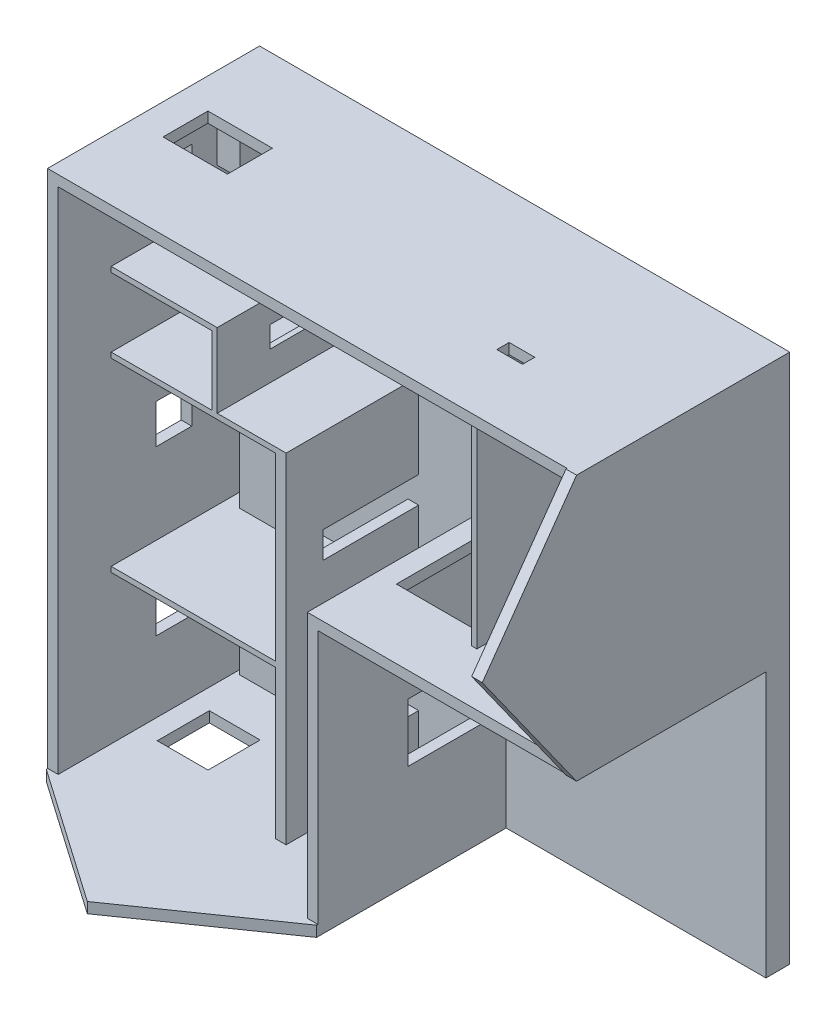
SolidWorks part; units mm, degrees
ref_plane "Front Plane" through (0, 0, 0) normal (0, 0, 1) x (1, 0, 0)
ref_plane "Top Plane" through (0, 0, 0) normal (0, 1, 0) x (1, 0, 0)
ref_plane "Right Plane" through (0, 0, 0) normal (1, 0, 0) x (0, 0, -1)
sketch "Sketch1" plane through (0, 0, 0) normal (0, 0, 1) x (1, 0, 0)
  line L0 (50, 50) -> (50, 48)
  line L1 (-50, -50) -> (50, -50)
  line L2 (-50, -50) -> (-50, 50)
  line L3 (-50, 50) -> (50, 50)
  line L4 (50, -50) -> (50, 50)
  line L5 (-50, -50) -> (50, 50) construction
  line L6 (-50, 50) -> (50, -50) construction
  line L7 (50, 48) -> (-50, 48)
  line L8 (50, 50) -> (50, 48)
  line L9 (-50, 48) -> (-48, 48)
  line L10 (-50, -50) -> (-48, -50)
  line L11 (-48, -50) -> (-48, 48)
  line L12 (50, 50) -> (50, 0)
  line L13 (50, 0) -> (20, 0)
  line L14 (20, 0) -> (20, 50)
  line L15 (-50, -50) -> (-15, -50)
  line L16 (50, 0) -> (50, 2)
  line L17 (50, 2) -> (20, 2)
  line L18 (50, 0) -> (48, 0)
  line L19 (48, 0) -> (48, 50)
  line L20 (-15, -50) -> (-15, 16)
  line L21 (-15, -17) -> (-50, -17)
  line L22 (-50, 16) -> (-15, 16)
  line L23 (-15, -50) -> (1, -50)
  line L24 (1, -50) -> (1, 0)
  line L25 (1, 0) -> (20, 0)
  line L26 (20, 2) -> (1, 2)
  line L27 (1, 2) -> (1, 0)
  line L28 (1, -50) -> (1, -48)
  line L29 (1, -48) -> (-50, -48)
  line L30 (-15, -50) -> (-17, -50)
  line L31 (-17, -50) -> (-17, 16)
  line L32 (20, 50) -> (21, 50)
  line L33 (21, 50) -> (21, 0)
  line L34 (-15, 16) -> (-15, 15)
  line L35 (-15, 15) -> (-50, 15)
  line L36 (-15, -17) -> (-15, -18)
  line L37 (-15, -18) -> (-50, -18)
  line L38 (1, -50) -> (-1, -50)
  line L39 (-1, -50) -> (-1, 0)
  line L40 (1, 2) -> (-1, 2)
  line L41 (-1, 2) -> (-1, 0)
  point P0 (0, 0)
  dimension "D1" = 100
  dimension "D2" = 100
  dimension "D3" = 2
  dimension "D4" = 2
  dimension "D5" = 2
  dimension "D6" = 50
  dimension "D7" = 30
  dimension "D8" = 2
  dimension "D9" = 2
  dimension "D10" = 35
  dimension "D11" = 33
  dimension "D12" = 33
  dimension "D13" = 16
  dimension "D14" = 50
  dimension "D15" = 2
  dimension "D16" = 2
  dimension "D17" = 1
  dimension "D18" = 1
  dimension "D19" = 1
  dimension "D20" = 2
  dimension "D21" = 50
extrude "Boss-Extrude1" add sketch "Sketch1" along normal blind 40 contours L1 L31 L29 L11 | L11 L29 L2 L1 | L31 L15 L20 L29 | L1 L39 L29 L20 | L39 L23 L24 L29 | L40 L41 L39 L29 L24 L27 region at (0, -49, 0) region at (-8, -49, 0) region at (0, -23, 0) region at (-16, -49, 0) region at (-32.5, -49, 0) region at (-49, -49, 0)
extrude "Boss-Extrude3" add sketch "Sketch1<19>" along normal blind 40 contours L11 L37 L2 L29 | L11 L35 L2 L21 | L37 L11 L21 L2 | L2 L22 L11 L7 | L35 L11 L22 L2 region at (-49, 32, 0) region at (-49, 15.5, 0) region at (-49, -1, 0) region at (-49, -17.5, 0) region at (-49, -33, 0)
sketch "Sketch1<19>" plane through (0, 0, 0) normal (0, 0, 1) x (1, 0, 0) same geometry as "Sketch1"
extrude "Boss-Extrude4" add sketch "Sketch1<20>" along normal blind 40 contours L7 L14 L3 L2 | L3 L33 L7 L19 | L33 L3 L14 L7 region at (34.5, 49, 0) region at (20.5, 49, 0) region at (-15, 49, 0)
sketch "Sketch1<20>" plane through (0, 0, 0) normal (0, 0, 1) x (1, 0, 0) same geometry as "Sketch1"
extrude "Boss-Extrude5" add sketch "Sketch1<21>" along normal blind 40 contours L19 L7 L0 L3 | L19 L17 L12 L7 | L19 L13 L4 L17 | L17 L33 L13 L19 | L26 L27 L25 L14 | L33 L17 L14 L13 region at (49, 49, 0) region at (49, 25, 0) region at (49, 1, 0) region at (34.5, 1, 0) region at (20.5, 1, 0) region at (10.5, 1, 0)
sketch "Sketch1<21>" plane through (0, 0, 0) normal (0, 0, 1) x (1, 0, 0) same geometry as "Sketch1"
extrude "Boss-Extrude6" add sketch "Sketch1<23>" along normal blind 30 contours L35 L31 L22 L11 region at (-32.5, 15.5, 0)
sketch "Sketch1<23>" plane through (0, 0, 0) normal (0, 0, 1) x (1, 0, 0) same geometry as "Sketch1"
extrude "Boss-Extrude7" add sketch "Sketch1<28>" along normal blind 30 contours L20 L35 L31 L21 | L35 L20 L22 L31 | L20 L37 L31 L29 region at (-16, 15.5, 0) region at (-16, -33, 0) region at (-16, -1, 0)
sketch "Sketch1<28>" plane through (0, 0, 0) normal (0, 0, 1) x (1, 0, 0) same geometry as "Sketch1"
extrude "Boss-Extrude9" add sketch "Sketch1<31>" along normal blind 5 contours L31 L35 L11 L21 | L31 L37 L11 L29 | L41 L40 L26 L14 L7 L11 L22 L20 L29 L39 | L7 L33 L17 L19 region at (34.5, 25, 0) region at (-10.3503, 17.2139, 0) region at (-32.5, -1, 0) region at (-32.5, -33, 0)
sketch "Sketch1<31>" plane through (0, 0, 0) normal (0, 0, 1) x (1, 0, 0) same geometry as "Sketch1"
sketch "Sketch5" plane through (0, 0, 5) normal (0, 0, 1) x (1, 0, 0)
  line L0 (-48, -17) -> (-48, -18)
  line L1 (-48, -18) -> (-17, -18)
  line L2 (-17, -18) -> (-17, -17)
  line L3 (-17, -17) -> (-48, -17)
extrude "Boss-Extrude10" add sketch "Sketch5" against normal blind 5
sketch "Sketch7" plane through (0, -17, 0) normal (0, -1, 0) x (1, 0, 0)
  line L0 (-17, 30) -> (-15, 30)
  line L7 (-17, 5) -> (-17, 0)
  line L8 (-17, 0) -> (-15, 0)
  line L9 (-15, 0) -> (-15, 5)
  line L10 (-15, 5) -> (-15, 30)
  line L11 (-15, 30) -> (-17, 30)
  line L12 (-17, 30) -> (-17, 5)
  line L13 (-17, 5) -> (-17, 0)
  line L14 (-17, 0) -> (-15, 0)
  line L15 (-15, 0) -> (-15, 5)
  line L16 (-15, 5) -> (-15, 30)
  line L18 (-17, 30) -> (-17, 5)
  dimension "D1" = 0
extrude "Boss-Extrude15" add sketch "Sketch7" along normal blind 5 contours L13 L14 L15 L16 L0 L18
sketch "Sketch8" plane through (-48, 0, 0) normal (1, 0, 0) x (0, 0, -1)
  line L0 (-5, -48) -> (-5, -19)
  line L1 (-5, -48) -> (-5, 15) construction
  line L2 (-5, -19) -> (-30, -19)
  line L3 (-40, -48) -> (-40, 48) construction
  line L4 (-40, -19) -> (-40, -20)
  line L5 (-5, -19) -> (-5, -20)
  line L9 (-5, -20) -> (-30, -20)
  line L10 (-30, -19) -> (-30, -20)
  dimension "D1" = 29
  dimension "D2" = 25
extrude "Boss-Extrude16" add sketch "Sketch8" along normal blind 31 contours L2 L10 L9 L0 region at (-48, -19.5, 17.5)
sketch "Sketch9" plane through (0, 0, 0) normal (0, 0, -1) x (-1, 0, 0)
  line L0 (-20, 48) -> (-21, 48)
  line L1 (-21, 48) -> (-21, 2)
  line L2 (-21, 2) -> (-20, 2)
  line L3 (-20, 2) -> (-20, 48)
extrude "Boss-Extrude17" add sketch "Sketch9" against normal blind 30
sketch "Sketch10" plane through (0, 0, 5) normal (0, 0, 1) x (1, 0, 0)
  line L0 (-48, 16) -> (-28, 16)
  line L1 (-48, 16) -> (-15, 16) construction
  line L2 (-28, 16) -> (-28, 30)
  line L3 (-28, 30) -> (-48, 30)
  line L4 (-48, 16) -> (-48, 48) construction
  line L5 (-48, 30) -> (-48, 29)
  line L6 (-48, 29) -> (-28, 29)
  line L7 (-28, 16) -> (-29, 16)
  line L8 (-29, 16) -> (-29, 29)
  line M6 (-48, 48) -> (-48, 16)
  dimension "D1" = 20
  dimension "D2" = 14
  dimension "D3" = 1
  dimension "D4" = 1
extrude "Boss-Extrude18" add sketch "Sketch10" along normal blind 25 contours L6 L2 L3 M6 | L8 L0 L2 L6 region at (-28.5, 22.5, 5) region at (-38, 29.5, 5)
sketch "Sketch11" plane through (-15, 0, 0) normal (1, 0, 0) x (0, 0, -1)
  line L0 (-5, -38.5606) -> (-5, -33.5606)
  line L1 (-5, -48) -> (-5, 16) construction
  line L2 (-5, -33.5606) -> (-23, -33.5606)
  line L3 (-5, -38.5606) -> (-23, -38.5606)
  line L4 (-23, -38.5606) -> (-23, -33.5606)
  line L5 (-5, 0) -> (-23, 0)
  line L6 (-23, 0) -> (-23, -5)
  line L7 (-23, -5) -> (-5, -5)
  line M8 (-5, -48) -> (-5, 16)
  dimension "D1" = 5
  dimension "D2" = 18
  dimension "D3" = 5
  dimension "D4" = 18
extrude "Cut-Extrude1" cut sketch "Sketch11" against normal blind 25 contours L4 L3 L2 M8 | L6 L7 L5 M8 region at (-15, -36.0606, 14) region at (-15, -2.5, 14)
sketch "Sketch12" plane through (-28, 0, 0) normal (1, 0, 0) x (0, 0, -1)
  line L0 (-5, 21.4951) -> (-5, 25.4951)
  line L1 (-5, 16) -> (-5, 30) construction
  line L2 (-5, 25.4951) -> (-20, 25.4951)
  line L3 (-20, 25.4951) -> (-20, 21.4951)
  line L4 (-20, 21.4951) -> (-5, 21.4951)
  dimension "D1" = 4
  dimension "D2" = 15
extrude "Cut-Extrude2" cut sketch "Sketch12" against normal blind 17
sketch "Sketch13" plane through (21, 0, 0) normal (1, 0, 0) x (0, 0, -1)
  line L0 (-5, 2) -> (-5, 7)
  line L1 (-5, 48) -> (-5, 2) construction
  line L2 (-5, 7) -> (-20, 7)
  line L3 (-20, 7) -> (-20, 2)
  line L4 (-30, 2) -> (-5, 2) construction
  line L5 (-20, 2) -> (-5, 2)
  dimension "D1" = 5
  dimension "D2" = 15
extrude "Cut-Extrude3" cut sketch "Sketch13" against normal blind 17
sketch "Sketch15" plane through (0, 2, 0) normal (0, 1, 0) x (1, 0, 0)
  line L0 (2.7962, -5) -> (13.7962, -5)
  line L1 (48, -5) -> (-1, -5) construction
  line L2 (13.7962, -5) -> (13.7962, -23)
  line L3 (13.7962, -23) -> (2.7962, -23)
  line L4 (2.7962, -23) -> (2.7962, -5)
  dimension "D1" = 11
  dimension "D2" = 18
extrude "Cut-Extrude7" cut sketch "Sketch15" against normal blind 22
sketch "Sketch17" plane through (0, 0, 0) normal (0, -1, 0) x (1, 0, 0)
  line L0 (50, 0) -> (50, 5)
  line L1 (50, 40) -> (50, 0) construction
  line L2 (50, 5) -> (1, 5)
  line L3 (1, 40) -> (1, 0) construction
  line L4 (1, 5) -> (1, 0)
  line L5 (50, 0) -> (1, 0) construction
  line L6 (50, 0) -> (1, 0)
  dimension "D1" = 5
extrude "Boss-Extrude20" add sketch "Sketch17" along normal blind 50
sketch "Sketch23" plane through (1, 0, 0) normal (1, 0, 0) x (0, 0, -1)
  line L0 (-5, -30.6786) -> (-23, -30.6786)
  line L1 (-5, -50) -> (-5, 0) construction
  line L2 (-23, -30.6786) -> (-23, -19.6786)
  line L3 (-23, -19.6786) -> (-5, -19.6786)
  line L4 (-5, -30.6786) -> (-5, -19.6786)
  dimension "D1" = 18
  dimension "D2" = 11
extrude "Cut-Extrude10" cut sketch "Sketch23" against normal blind 6
sketch "Sketch24" plane through (0, 0, 0) normal (0, -1, 0) x (1, 0, 0)
  line L0 (13.7962, 5) -> (17.6537, 5)
  line L1 (50, 5) -> (13.7962, 5) construction
  line L2 (17.6537, 5) -> (17.6537, 23)
  line L3 (17.6537, 23) -> (13.7962, 23)
  line L4 (13.7962, 23) -> (13.7962, 5)
  dimension "D1" = 18
extrude "Cut-Extrude11" cut sketch "Sketch24" against normal blind 6
sketch "Sketch25" plane through (0, 0, 0) normal (0, -1, 0) x (1, 0, 0)
  line L0 (17.6537, 23) -> (17.6537, 27)
  line L1 (17.6537, 27) -> (2.7962, 27)
  line L2 (2.7962, 27) -> (2.7962, 23)
  line L3 (2.7962, 23) -> (17.6537, 23)
  dimension "D1" = 4
extrude "Cut-Extrude12" cut sketch "Sketch25" against normal blind 6
sketch "Sketch26" plane through (0, 0, 0) normal (0, -1, 0) x (1, 0, 0)
  line L0 (27.3061, 27.4895) -> (39.6317, 27.4895)
  line L1 (39.6317, 27.4895) -> (39.6317, 19.0347)
  line L2 (39.6317, 19.0347) -> (27.3061, 19.0347)
  line L3 (27.3061, 19.0347) -> (27.3061, 27.4895)
extrude "Cut-Extrude13" cut sketch "Sketch26" against normal blind 6
sketch "Sketch29" plane through (-50, 0, 0) normal (-1, 0, 0) x (0, 0, 1)
  line L5 (14.7979, 3.7003) -> (21.5327, 3.7003)
  line L6 (14.7979, 3.7003) -> (14.7979, -3.7003)
  line L11 (14.7979, -3.7003) -> (21.5327, -3.7003)
  line L12 (21.5327, 3.7003) -> (21.5327, -3.7003)
  line L17 (14.7979, 3.7003) -> (21.5327, -3.7003) construction
  line L18 (14.7979, -3.7003) -> (21.5327, 3.7003) construction
  line L19 (14.7979, -27.6046) -> (21.5327, -27.6046)
  line L20 (14.7979, -27.6046) -> (14.7979, -34.6008)
  line L21 (14.7979, -34.6008) -> (21.5327, -34.6008)
  line L22 (21.5327, -27.6046) -> (21.5327, -34.6008)
  line L23 (14.7979, -27.6046) -> (21.5327, -34.6008) construction
  line L24 (14.7979, -34.6008) -> (21.5327, -27.6046) construction
  line L25 (14.7979, 35.5253) -> (21.5327, 35.5253)
  line L26 (14.7979, 35.5253) -> (14.7979, 42.3474)
  line L27 (14.7979, 42.3474) -> (21.5327, 42.3474)
  line L28 (21.5327, 35.5253) -> (21.5327, 42.3474)
  line L29 (14.7979, 35.5253) -> (21.5327, 42.3474) construction
  line L30 (14.7979, 42.3474) -> (21.5327, 35.5253) construction
  point P0 (18.1653, 0)
  point P5 (18.1653, -31.1027)
  point P10 (18.1653, 38.9363)
extrude "Cut-Extrude18" cut sketch "Sketch29" against normal blind 6
sketch "Sketch30" plane through (0, -50, 0) normal (0, -1, 0) x (1, 0, 0)
  line L1 (-44.162, 25.1479) -> (-34.5784, 25.1479)
  line L2 (-44.162, 25.1479) -> (-44.162, 15.3213)
  line L3 (-44.162, 15.3213) -> (-34.5784, 15.3213)
  line L4 (-34.5784, 25.1479) -> (-34.5784, 15.3213)
  line L5 (-44.162, 25.1479) -> (-34.5784, 15.3213) construction
  line L6 (-44.162, 15.3213) -> (-34.5784, 25.1479) construction
  point P0 (-39.3702, 20.2346)
extrude "Cut-Extrude19" cut sketch "Sketch30" against normal blind 6
sketch "Sketch32" plane through (0, 0, 5) normal (0, 0, 1) x (1, 0, 0)
  line L0 (-17, -20) -> (-48, -20) construction
  line L1 (-42.7475, 2.9062) -> (-33.4614, 2.9062)
  line L2 (-42.7475, 2.9062) -> (-42.7475, -16.3961)
  line L3 (-42.7475, -16.3961) -> (-33.4614, -16.3961)
  line L4 (-33.4614, 2.9062) -> (-33.4614, -16.3961)
  line L5 (-42.7475, 2.9062) -> (-33.4614, -16.3961) construction
  line L6 (-42.7475, -16.3961) -> (-33.4614, 2.9062) construction
  line L7 (-33.4614, -43.6108) -> (-42.7475, -43.6108)
  line L8 (-33.4614, -43.6108) -> (-33.4614, -20)
  line L9 (-33.4614, -20) -> (-42.7475, -20)
  line L10 (-42.7475, -43.6108) -> (-42.7475, -20)
  line L11 (-33.4614, -43.6108) -> (-42.7475, -20) construction
  line L12 (-33.4614, -20) -> (-42.7475, -43.6108) construction
  point P0 (-38.1044, -6.7449)
  point P5 (-38.1044, -31.8054)
extrude "Boss-Extrude23" add sketch "Sketch32" along normal blind 6
sketch "Sketch34" plane through (0, 0, 5) normal (0, 0, 1) x (1, 0, 0)
  circle A0 centre (-2.9001, 39.2771) radius 4.9713
extrude "Boss-Extrude25" add sketch "Sketch34" along normal blind 6
sketch "Sketch35" plane through (0, 0, 5) normal (0, 0, 1) x (1, 0, 0)
  line L1 (4.447, 41.0368) -> (7.1288, 41.0368)
  line L2 (4.447, 41.0368) -> (4.447, 37.9126)
  line L3 (4.447, 37.9126) -> (7.1288, 37.9126)
  line L4 (7.1288, 41.0368) -> (7.1288, 37.9126)
  line L5 (4.447, 41.0368) -> (7.1288, 37.9126) construction
  line L6 (4.447, 37.9126) -> (7.1288, 41.0368) construction
  line L7 (-12.4697, 42.5989) -> (-10.1161, 42.5989)
  line L8 (-12.4697, 42.5989) -> (-12.4697, 39.4747)
  line L9 (-12.4697, 39.4747) -> (-10.1161, 39.4747)
  line L10 (-10.1161, 42.5989) -> (-10.1161, 39.4747)
  line L11 (-12.4697, 42.5989) -> (-10.1161, 39.4747) construction
  line L12 (-12.4697, 39.4747) -> (-10.1161, 42.5989) construction
  point P0 (5.7879, 39.4747)
  point P5 (-11.2929, 41.0368)
extrude "Boss-Extrude26" add sketch "Sketch35" along normal blind 3
sketch "Sketch36" plane through (0, -50, 0) normal (0, -1, 0) x (1, 0, 0)
  line L1 (-11.6148, 24.721) -> (-2.42, 24.721)
  line L2 (-11.6148, 24.721) -> (-11.6148, 16.1666)
  line L3 (-11.6148, 16.1666) -> (-2.42, 16.1666)
  line L4 (-2.42, 24.721) -> (-2.42, 16.1666)
  line L5 (-11.6148, 24.721) -> (-2.42, 16.1666) construction
  line L6 (-11.6148, 16.1666) -> (-2.42, 24.721) construction
  point P0 (-7.0174, 20.4438)
extrude "Cut-Extrude20" cut sketch "Sketch36" against normal blind 13
sketch "Sketch40" plane through (0, 0, 40) normal (0, 0, 1) x (1, 0, 0)
  line L0 (48, 2) -> (48, 0)
  line L1 (50, 0) -> (1, 0) construction
  line L2 (48, 0) -> (50, 0)
  line L3 (50, 0) -> (50, 50)
  line L4 (50, 50) -> (48, 50)
  line L5 (-50, 50) -> (50, 50) construction
  line L6 (48, 50) -> (48, 48)
  line L7 (48, 48) -> (48, 0)
  line M7 (1, 0) -> (50, 0)
  line M8 (50, 0) -> (50, 50)
  line M9 (50, 50) -> (-50, 50)
  line M12 (48, 48) -> (48, 2)
extrude "Boss-Extrude28" add sketch "Sketch40" along normal blind 18 contours L6 L0 M9 M12 M7 M8 region at (49, 25, 40)
sketch "Sketch41" plane through (50, 0, 0) normal (1, 0, 0) x (0, 0, -1)
  line L0 (-58, 50) -> (-58, 25)
  line L1 (-58, 0) -> (-58, 50) construction
  line L2 (-58, 25) -> (-58, 0)
  line L3 (-58, 0) -> (-40.2114, 0)
  line L4 (-58, 0) -> (-5, 0) construction
  line L5 (-40.2114, 0) -> (-58, 25)
  line L6 (-58, 50) -> (-40.2114, 50)
  line L7 (-58, 50) -> (0, 50) construction
  line L8 (-40.2114, 50) -> (-58, 25)
  line M8 (0, 50) -> (-58, 50)
  line M9 (-58, 50) -> (-58, 0)
  line M10 (-58, 0) -> (-5, 0)
extrude "Cut-Extrude22" cut sketch "Sketch41" against normal blind 18 contours L8 M8 M9 | L5 M10 M9 region at (50, 41.6667, 52.0705) region at (50, 8.3333, 52.0705)
sketch "Sketch42" plane through (0, 0, 40) normal (0, 0, 1) x (1, 0, 0)
  line L0 (-1, -48) -> (1, -48)
  line L1 (1, -50) -> (1, 0) construction
  line L2 (1, -48) -> (1, -50)
  line L3 (1, -50) -> (-50, -50)
  line L4 (-50, -50) -> (-50, -48)
  line L5 (-50, -50) -> (-50, 50) construction
  line L6 (-50, -48) -> (-48, -48)
  line L7 (-48, -48) -> (-1, -48)
extrude "Boss-Extrude29" add sketch "Sketch42" along normal blind 18
sketch "Sketch43" plane through (0, -50, 0) normal (0, -1, 0) x (1, 0, 0)
  line L1 (-50, 58) -> (1, 58) construction
  line L2 (-24.5, 58) -> (-50, 58)
  line L3 (-50, 58) -> (-50, 40.2458)
  line L4 (-50, 58) -> (-50, 0) construction
  line L9 (-24.5, 58) -> (-50, 40.2458)
  line L10 (-24.5, 58) -> (1, 58)
  line L11 (1, 58) -> (1, 40.2458)
  line L12 (1, 58) -> (1, 5) construction
  line L13 (1, 40.2458) -> (-24.5, 58)
  line M12 (1, 5) -> (1, 58)
  line M13 (1, 58) -> (-50, 58)
  line M14 (-50, 58) -> (-50, 0)
extrude "Cut-Extrude23" cut sketch "Sketch43" against normal blind 18 contours L9 M13 M14 | L13 M12 M13 region at (-41.5, -50, 52.0819) region at (-7.5, -50, 52.0819)
sketch "Sketch47" plane through (0, 0, 5) normal (0, 0, 1) x (1, 0, 0)
  line L0 (48, 48) -> (48, 38)
  line L1 (48, 2) -> (48, 48) construction
  line L2 (48, 38) -> (28, 38)
  line L3 (28, 38) -> (28, 48)
  line L4 (48, 48) -> (21, 48) construction
  line L5 (28, 48) -> (48, 48)
  line L6 (28, 48) -> (29, 48)
  line L7 (29, 48) -> (29, 38)
  line L8 (48, 38) -> (48, 39)
  line L9 (48, 39) -> (29, 39)
  dimension "D1" = 20
  dimension "D2" = 10
  dimension "D3" = 1
  dimension "D4" = 1
extrude "Boss-Extrude32" add sketch "Sketch47" along normal blind 25 contours L7 L5 L3 L2 | L0 L9 L7 L2 region at (38.5, 38.5, 5) region at (28.5, 43, 5)
sketch "Sketch48" plane through (28, 0, 0) normal (-1, 0, 0) x (0, 0, 1)
  line L0 (5, 41.8964) -> (23, 41.8964)
  line L1 (5, 38) -> (5, 48) construction
  line L2 (23, 41.8964) -> (23, 44.8964)
  line L3 (23, 44.8964) -> (5.0879, 44.8964)
  line L4 (5.0879, 44.8964) -> (5, 41.8964)
  point P8 (5.2388, 43.8195)
  dimension "D1" = 3
extrude "Cut-Extrude24" cut sketch "Sketch48" against normal blind 11
sketch "Sketch50" plane through (0, 0, 5) normal (0, 0, 1) x (1, 0, 0)
  line L0 (47.0235, 2.9885) -> (35.0235, 2.9885)
  line L5 (35.0235, 2.9885) -> (35.0235, 23.3773)
  line L6 (35.0235, 23.3773) -> (47.0235, 23.3773)
  line L7 (47.0235, 23.3773) -> (47.0235, 2.9885)
  point P0 (38.6725, 13.863)
  dimension "D1" = 12
  dimension "D2" = 12
extrude "Boss-Extrude34" add sketch "Sketch50" along normal blind 6
sketch "Sketch53" plane through (0, 48, 0) normal (0, -1, 0) x (1, 0, 0)
  line L1 (21.9606, 27.2128) -> (26.7998, 27.2128)
  line L2 (21.9606, 27.2128) -> (21.9606, 24.8909)
  line L3 (21.9606, 24.8909) -> (26.7998, 24.8909)
  line L4 (26.7998, 27.2128) -> (26.7998, 24.8909)
  line L5 (21.9606, 27.2128) -> (26.7998, 24.8909) construction
  line L6 (21.9606, 24.8909) -> (26.7998, 27.2128) construction
  point P0 (24.3802, 26.0519)
extrude "Cut-Extrude28" cut sketch "Sketch53" against normal blind 6
sketch "Sketch54" plane through (0, 50, 0) normal (0, 1, 0) x (1, 0, 0)
  line L1 (-32.102, -23.9685) -> (-44.255, -23.9685)
  line L2 (-32.102, -23.9685) -> (-32.102, -15.4916)
  line L3 (-32.102, -15.4916) -> (-44.255, -15.4916)
  line L4 (-44.255, -23.9685) -> (-44.255, -15.4916)
  line L5 (-32.102, -23.9685) -> (-44.255, -15.4916) construction
  line L6 (-32.102, -15.4916) -> (-44.255, -23.9685) construction
  point P0 (-38.1785, -19.73)
extrude "Cut-Extrude29" cut sketch "Sketch54" against normal blind 6
sketch "Sketch55" plane through (0, 0, 5) normal (0, 0, 1) x (1, 0, 0)
  line L0 (-48, 48) -> (-43.679, 48)
  line L1 (20, 48) -> (-48, 48) construction
  line L2 (-43.679, 48) -> (-43.679, 36.5252)
  line L3 (-43.679, 36.5252) -> (-48, 36.5252)
  line L4 (-48, 30) -> (-48, 48) construction
  line L5 (-48, 36.5252) -> (-48, 48)
extrude "Boss-Extrude36" add sketch "Sketch55" along normal blind 5
sketch "Sketch56" plane through (0, -50, 0) normal (0, -1, 0) x (1, 0, 0)
  circle A1 centre (-24.3212, 45.1269) radius 3.5814
  dimension "D1" = 7.1628
extrude "Cut-Extrude30" cut sketch "Sketch56" against normal blind 0.5
sketch "Sketch57" plane through (0, 0, 5) normal (0, 0, 1) x (1, 0, 0)
  line L0 (1, -50) -> (1, 0)
  line L1 (1, 0) -> (50, 0)
  line L2 (50, 0) -> (50, -50)
  line L3 (50, -50) -> (1, -50)
extrude "Cut-Extrude31" cut sketch "Sketch57" against normal blind 0.5
